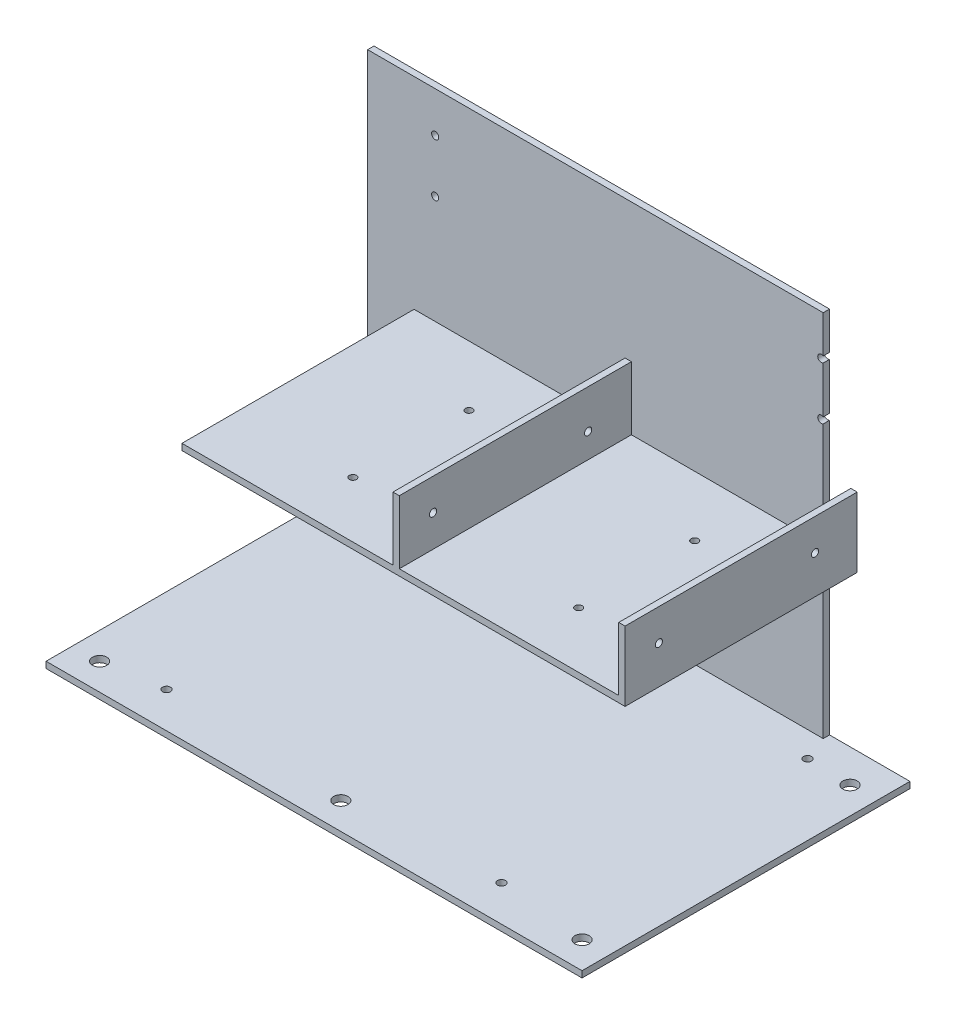
SolidWorks part; units mm, degrees
ref_plane "Front Plane" through (0, 0, 0) normal (0, 0, 1) x (1, 0, 0)
ref_plane "Top Plane" through (0, 0, 0) normal (0, 1, 0) x (1, 0, 0)
ref_plane "Right Plane" through (0, 0, 0) normal (1, 0, 0) x (0, 0, -1)
sketch "Sketch1" plane through (0, 0, 0) normal (0, 1, 0) x (1, 0, 0)
  line L1 (0, 0) -> (254, 0)
  line L2 (0, 0) -> (0, -152.4)
  line L3 (0, -152.4) -> (254, -152.4)
  line L4 (254, 0) -> (254, -152.4)
  dimension "D1" = 254
  dimension "D2" = 152.4
extrude "Boss-Extrude1" add sketch "Sketch1" along normal blind 3
sketch "Sketch2" plane through (0, 0, 0) normal (0, 0, -1) x (-1, 0, 0)
  line L1 (-254, 0) -> (0, 0)
  line L2 (-254, 0) -> (-254, 177.8)
  line L3 (-254, 177.8) -> (0, 177.8)
  line L4 (0, 0) -> (0, 177.8)
  dimension "D1" = 177.8
extrude "Boss-Extrude2" add sketch "Sketch2" along normal blind 3
sketch "Sketch3" plane through (0, 0, 0) normal (0, 0, 1) x (1, 0, 0)
  line L0 (25, 90.7404) -> (25, 110.8404) construction
  line L1 (22, 112.2404) -> (232, 112.2404)
  line L2 (22, 112.2404) -> (22, 79.2404)
  line L3 (22, 79.2404) -> (232, 79.2404)
  line L4 (232, 112.2404) -> (232, 79.2404)
  line L8 (172.7, 82.2404) -> (227.6, 82.2404) construction
  line L9 (229, 83.6404) -> (229, 110.8404) construction
  dimension "D1" = 3
  dimension "D2" = 3
  dimension "D3" = 3
extrude "Boss-Extrude3" add sketch "Sketch3" along normal blind 110
sketch "Sketch4" plane through (0, 0, 110) normal (0, 0, 1) x (1, 0, 0)
  line L0 (232, 112.2404) -> (22, 112.2404) construction
  line L1 (229, 82.2404) -> (125, 82.2404)
  line L2 (229, 82.2404) -> (229, 112.2404)
  line L3 (229, 112.2404) -> (125, 112.2404)
  line L4 (125, 82.2404) -> (125, 112.2404)
  line L5 (232, 79.2404) -> (232, 112.2404) construction
  line L6 (122, 82.2404) -> (22, 82.2404)
  line L7 (122, 82.2404) -> (122, 112.2404)
  line L8 (122, 112.2404) -> (22, 112.2404)
  line L9 (22, 82.2404) -> (22, 112.2404)
  line L10 (22, 79.2404) -> (232, 79.2404) construction
  line L11 (22, 79.2404) -> (232, 79.2404) construction
  line L12 (122, 83.6404) -> (122, 110.8404) construction
  line L13 (22, 112.2404) -> (22, 79.2404) construction
  dimension "D1" = 3
  dimension "D2" = 3
  dimension "D3" = 3
  dimension "D4" = 3
  dimension "D5" = 3
extrude "Cut-Extrude1" cut sketch "Sketch4" against normal blind 110
hole_wizard "#6 Clearance Hole1" positions "Sketch8" profile "Sketch9" hole size "#6" standard "ANSI Inch" end condition up to next
sketch "Sketch8" plane through (0, 0, 0) normal (0, -1, 0) x (-1, 0, 0)
  point P0 (-40.113, -11.985)
  point P4 (-40.113, -135.429)
  point P7 (-220.453, -11.985)
  point P10 (-198.863, -135.429)
sketch "Sketch9" plane through (40.113, 0, 11.985) normal (1, 0, 0) x (0, 0, -1)
  line L0 (0, 0) -> (0, 3)
  line L1 (0, 3) -> (1.8986, 3)
  line L2 (1.8986, 3) -> (1.8986, 0)
  line L5 (1.8986, 0) -> (0, 0)
  line L11 (0, -6.35) -> (0, 107.95) construction
  dimension "Thru Hole Dia." = 3.7973
  dimension "Thru Hole Depth" = 3
hole_wizard "M3 Clearance Hole1" positions "Sketch12" profile "Sketch13" hole size "M3" standard "ANSI Metric" end condition up to next
sketch "Sketch12" plane through (0, 79.2404, 0) normal (0, -1, 0) x (-1, 0, 0)
  point P0 (-76.5, -28.5)
  point P3 (-76.5, -83.5)
  point P6 (-183.5, -83.5)
  point P9 (-183.5, -28.5)
sketch "Sketch13" plane through (76.5, 79.2404, 28.5) normal (1, 0, 0) x (0, 0, -1)
  line L0 (0, 0) -> (0, 3)
  line L1 (0, 3) -> (1.7, 3)
  line L2 (1.7, 3) -> (1.7, 0)
  line L5 (1.7, 0) -> (0, 0)
  line L11 (0, -6.35) -> (0, 107.95) construction
  dimension "Thru Hole Dia." = 3.4
  dimension "Thru Hole Depth" = 3
hole_wizard "M3 Clearance Hole2" positions "Sketch14" profile "Sketch15" hole size "M3" standard "ANSI Metric" end condition up to next
sketch "Sketch14" plane through (125, 0, 0) normal (1, 0, 0) x (0, 0, -1)
  point P0 (-94, 97.2404)
  point P3 (-20.5069, 93.8291)
sketch "Sketch15" plane through (125, 97.2404, 94) normal (0, 1, 0) x (0, 0, -1)
  line L0 (0, 0) -> (0, 3)
  line L1 (0, 3) -> (1.7, 3)
  line L2 (1.7, 3) -> (1.7, 0)
  line L5 (1.7, 0) -> (0, 0)
  line L11 (0, -6.35) -> (0, 107.95) construction
  dimension "Thru Hole Dia." = 3.4
  dimension "Thru Hole Depth" = 3
hole_wizard "M3 Clearance Hole3" positions "Sketch18" profile "Sketch19" hole size "M3" standard "ANSI Metric" end condition up to next
sketch "Sketch18" plane through (232, 0, 0) normal (1, 0, 0) x (0, 0, -1)
  point P0 (-94, 97.2404)
  point P3 (-20, 97.2404)
sketch "Sketch19" plane through (232, 97.2404, 94) normal (0, 1, 0) x (0, 0, -1)
  line L0 (0, 0) -> (0, 3)
  line L1 (0, 3) -> (1.7, 3)
  line L2 (1.7, 3) -> (1.7, 0)
  line L5 (1.7, 0) -> (0, 0)
  line L11 (0, -6.35) -> (0, 107.95) construction
  dimension "Thru Hole Dia." = 3.4
  dimension "Thru Hole Depth" = 3
hole_wizard "1/4 Clearance Hole1" positions "Sketch22" profile "Sketch23" hole size "1/4" standard "ANSI Inch" end condition up to next
sketch "Sketch22" plane through (0, 3, 0) normal (0, 1, 0) x (1, 0, 0)
  line L13 (254, -139.7) -> (0, -139.7) construction
  line L15 (254, -76.2) -> (0, -76.2) construction
  line L16 (254, -152.4) -> (254, 0) construction
  line L17 (0, 0) -> (0, -152.4) construction
  line L21 (0, -152.4) -> (254, -152.4) construction
  line L23 (127, -152.4) -> (127, 0) construction
  line L24 (254, 0) -> (0, 0) construction
  point P93 (241.3, -139.7)
  point P96 (12.7, -139.7)
  point P98 (12.7, -12.7)
  point P99 (241.3, -12.7)
  point P100 (127, -139.7)
  point P102 (244.4898, -272.9773)
  point P105 (0, 0)
  point P106 (279.4, -139.6543)
  dimension "D1" = 114.3
  dimension "D2" = 12.7
sketch "Sketch23" plane through (244.4898, 3, 272.9773) normal (1, 0, 0) x (0, 0, 1)
  line L0 (0, 0) -> (0, 3)
  line L1 (0, 3) -> (3.3782, 3)
  line L2 (3.3782, 3) -> (3.3782, 0)
  line L5 (3.3782, 0) -> (0, 0)
  line L11 (0, -6.35) -> (0, 107.95) construction
  dimension "Thru Hole Dia." = 6.7564
  dimension "Thru Hole Depth" = 3
hole_wizard "M3 Clearance Hole4" positions "Sketch24" profile "Sketch25" hole size "M3" standard "ANSI Metric" end condition up to next
sketch "Sketch24" plane through (0, 0, 0) normal (0, 0, 1) x (1, 0, 0)
  point P0 (32, 158.5904)
  point P3 (32, 133.5904)
  point P6 (215, 158.5904)
  point P9 (215, 133.5904)
sketch "Sketch25" plane through (32, 158.5904, 0) normal (1, 0, 0) x (0, -1, 0)
  line L0 (0, 0) -> (0, 3)
  line L1 (0, 3) -> (1.7, 3)
  line L2 (1.7, 3) -> (1.7, 0)
  line L5 (1.7, 0) -> (0, 0)
  line L11 (0, -6.35) -> (0, 107.95) construction
  dimension "Thru Hole Dia." = 3.4
  dimension "Thru Hole Depth" = 3
sketch "Sketch26" plane through (0, 0, 0) normal (0, 0, 1) x (1, 0, 0)
  line L2 (215.9, 3) -> (215.9, 177.8)
  line L7 (254, 3) -> (0, 3) construction
  line L8 (0, 177.8) -> (254, 177.8) construction
  line L9 (215.9, 177.8) -> (254, 177.8)
  line L10 (254, 177.8) -> (254, 3)
  line L11 (254, 3) -> (215.9, 3)
  dimension "D1" = 38.1
extrude "Cut-Extrude2" cut sketch "Sketch26" against normal up to next
ref_axis "Axis1" through (241.3, 0, 139.7) along (0, 1, 0)
ref_axis "Axis2" through (12.7, 0, 139.7) along (0, 1, 0)
